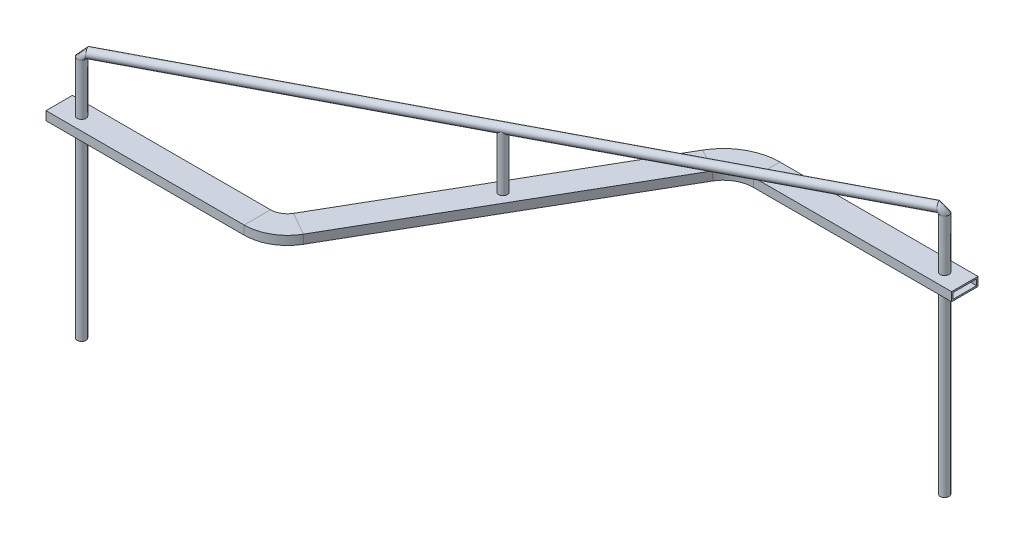
SolidWorks part; units mm, degrees
ref_plane "前视基准面" through (0, 0, 0) normal (0, 0, 1) x (1, 0, 0)
ref_plane "上视基准面" through (0, 0, 0) normal (0, 1, 0) x (1, 0, 0)
ref_plane "右视基准面" through (0, 0, 0) normal (1, 0, 0) x (0, 0, -1)
sketch "草图1" plane through (0, 0, 0) normal (1, 0, 0) x (0, 0, -1)
  line L0 (-80, 20) -> (80, 20)
  line L1 (-90, -30) -> (90, -30)
  line L2 (-90, -30) -> (-90, 30)
  line L3 (-90, 30) -> (90, 30)
  line L4 (90, -30) -> (90, 30)
  line L5 (-90, -30) -> (90, 30) construction
  line L6 (-90, 30) -> (90, -30) construction
  line L7 (80, -20) -> (80, 20)
  line L8 (-80, -20) -> (80, -20)
  line L9 (-80, -20) -> (-80, 20)
  point P0 (0, 0)
  dimension "D1" = 180
  dimension "D2" = 60
  dimension "D3" = 10
sketch "草图2" plane through (0, 0, 0) normal (0, 1, 0) x (1, 0, 0)
  line L0 (0, -90) -> (-1350, -90)
  line L1 (0, -90) -> (0, 90) construction
  line L2 (-2803.0127, -2106.6918) -> (-4153.0127, -2106.6918)
  line L3 (-1527.5352, -192.5) -> (-2547.5352, -1959.1918)
  arc A0 (-1350, -90) -> (-1527.5352, -192.5) centre (-1350, -295) ccw
  arc A1 (-2803.0127, -2106.6918) -> (-2547.5352, -1959.1918) centre (-2803.0127, -1811.6918) ccw
  point P6 (-2037.5352, -1075.8459)
  dimension "D2" = 1350
  dimension "D3" = 410
  dimension "D4" = 205
  dimension "D6" = 590
  dimension "D1" = 1350
  dimension "D5" = 2040
sweep "扫描1" add profiles "草图1" path "草图2"
sketch "草图3" plane through (0, 30, 0) normal (0, 1, 0) x (1, 0, 0)
  line L0 (-1683.4198, -102.5) -> (-2703.4198, -1869.1918) construction
  line L1 (-4000.8357, -2016.6918) -> (-2115.4775, -1030.8459) construction
  line L2 (-2132.2937, -1039.639) -> (-19.9801, 64.8809) construction
  circle A0 centre (-4000.8357, -2016.6918) radius 30
  circle A1 centre (-2115.4775, -1030.8459) radius 30
  circle A2 centre (-139.8759, 2.1879) radius 30
  dimension "D1" = 90
extrude "凸台-拉伸1" add sketch "草图3" along normal blind 350
sketch "草图4" plane through (0, 380, 0) normal (0, 1, 0) x (1, 0, 0)
  circle A0 centre (-4000.8357, -2016.6918) radius 30
ref_plane "基准面1" through (-17.0305, 0, -32.5695) normal (0.4634, 0, 0.8862) x (0.8862, 0, -0.4634)
sketch "草图5" plane through (-17.0305, 0, -32.5695) normal (0.4634, 0, 0.8862) x (0.8862, 0, -0.4634)
  arc A0 (-4449.8746, 410) -> (-4479.8746, 380) centre (-4449.8746, 380) ccw
  dimension "D1" = 60
sweep "扫描2" add profiles "草图4" path "草图5"
sketch "草图6" plane through (0, 380, 0) normal (0, 1, 0) x (1, 0, 0)
  circle A0 centre (-139.8759, 2.1879) radius 30
sketch "草图7" plane through (-17.0305, 0, -32.5695) normal (0.4634, 0, 0.8862) x (0.8862, 0, -0.4634)
  arc A0 (-122.9392, 380) -> (-152.9392, 410) centre (-152.9392, 380) ccw
  dimension "D1" = 60
sweep "扫描3" add profiles "草图6" path "草图7"
sketch "草图9" plane through (0, 380, 0) normal (0, 1, 0) x (1, 0, 0)
  circle A0 centre (-2115.4775, -1030.8459) radius 30
extrude "凸台-拉伸3" add sketch "草图9" along normal blind 30
sketch "草图10" plane through (-135.5293, 0, 70.8677) normal (-0.8862, 0, 0.4634) x (0.4634, 0, 0.8862)
  circle A0 centre (-66.7533, 410) radius 30
extrude "凸台-拉伸5" add sketch "草图10" along normal up to surface (4296.9353 mm away) separate body up to face at (-3974.2509, 380, 2002.7904)
sketch "草图11" plane through (0, 30, 0) normal (0, 1, 0) x (1, 0, 0)
  circle A0 centre (-4000.8357, -2016.6918) radius 30
  circle A1 centre (-139.8759, 2.1879) radius 30
extrude "凸台-拉伸6" add sketch "草图11" against normal blind 1310
